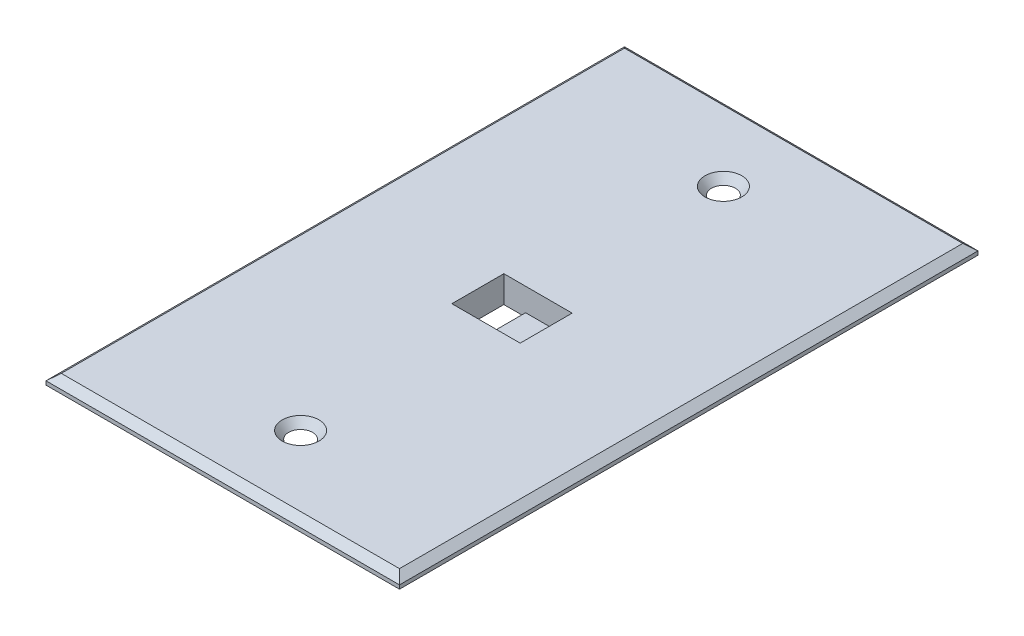
SolidWorks part; units mm, degrees
ref_plane "Front Plane" through (0, 0, 0) normal (0, 0, 1) x (1, 0, 0)
ref_plane "Top Plane" through (0, 0, 0) normal (0, 1, 0) x (1, 0, 0)
ref_plane "Right Plane" through (0, 0, 0) normal (1, 0, 0) x (0, 0, -1)
sketch "Sketch1" plane through (0, 0, 0) normal (0, 1, 0) x (1, 0, 0)
  line L1 (-34.675, 56.75) -> (34.675, 56.75)
  line L2 (-34.675, 56.75) -> (-34.675, -56.75)
  line L3 (-34.675, -56.75) -> (34.675, -56.75)
  line L4 (34.675, 56.75) -> (34.675, -56.75)
  line L5 (-34.675, 56.75) -> (34.675, -56.75) construction
  line L6 (-34.675, -56.75) -> (34.675, 56.75) construction
  point P0 (0, 0)
  dimension "D1" = 113.5
  dimension "D2" = 69.35
extrude "Boss-Extrude5" add sketch "Sketch1" along normal blind 2 contours L2 L1 L4 L3
sketch "Sketch2" plane through (0, 2, 0) normal (0, 1, 0) x (1, 0, 0)
  line L0 (0, 56.75) -> (0, -56.75) construction
  line L1 (-34.675, 56.75) -> (34.675, 56.75) construction
  line L2 (-34.675, -56.75) -> (34.675, -56.75) construction
  line L3 (-34.675, 0) -> (34.675, 0) construction
  line L4 (-34.675, 56.75) -> (-34.675, -56.75) construction
  line L5 (34.675, 56.75) -> (34.675, -56.75) construction
  circle A0 centre (0, 41.476) radius 2.35
  circle A1 centre (0, -41.476) radius 2.35
extrude "Cut-Extrude3" cut sketch "Sketch2" against normal blind 2.5
chamfer "face chamfer" distance 1.5 angle 40 6 edges at (0, 2, 39.126) (0, 2, -39.126) (0, 2, -56.75) (34.675, 2, 0) (0, 2, 56.75) (-34.675, 2, 0)
sketch "Sketch4" plane through (0, 0, 0) normal (0, -1, 0) x (-1, 0, 0)
  line L1 (-30.1192, 45.2572) -> (30.1192, 45.2572)
  line L2 (-30.1192, 45.2572) -> (-30.1192, -45.2572)
  line L3 (-30.1192, -45.2572) -> (30.1192, -45.2572)
  line L4 (30.1192, 45.2572) -> (30.1192, -45.2572)
  line L5 (-30.1192, 45.2572) -> (30.1192, -45.2572) construction
  line L6 (-30.1192, -45.2572) -> (30.1192, 45.2572) construction
  point P0 (0, 0)
extrude "Cut-Extrude6" cut sketch "Sketch4" against normal blind 0.5
sketch "Sketch5" plane through (0, 2, 0) normal (0, 1, 0) x (1, 0, 0)
  line L0 (-33.175, 0) -> (33.175, 0) construction
  line L1 (-33.175, 55.25) -> (-33.175, -55.25) construction
  line L2 (33.175, -55.25) -> (33.175, 55.25) construction
  line L3 (0, 55.25) -> (0, -56.75) construction
  line L4 (33.175, 55.25) -> (-33.175, 55.25) construction
  line L5 (34.675, -56.75) -> (-34.675, -56.75) construction
  line L7 (-6.7, 5.1) -> (6.7, 5.1)
  line L8 (-6.7, 5.1) -> (-6.7, -5.1)
  line L9 (-6.7, -5.1) -> (6.7, -5.1)
  line L10 (6.7, 5.1) -> (6.7, -5.1)
  line L11 (-6.7, 5.1) -> (6.7, -5.1) construction
  line L12 (-6.7, -5.1) -> (6.7, 5.1) construction
  line L13 (10.4666, 8.5495) -> (-10.4666, 8.5495)
  line L14 (10.4666, 8.5495) -> (10.4666, -8.5495)
  line L15 (10.4666, -8.5495) -> (-10.4666, -8.5495)
  line L16 (-10.4666, 8.5495) -> (-10.4666, -8.5495)
  line L17 (10.4666, 8.5495) -> (-10.4666, -8.5495) construction
  line L18 (10.4666, -8.5495) -> (-10.4666, 8.5495) construction
  point P12 (0, 0)
  point P17 (0, 0)
  dimension "D1" = 13.4
  dimension "D2" = 10.2
extrude "Boss-Extrude7" add sketch "Sketch5" against normal blind 4.5
sketch "Sketch6" plane through (0, 2, 0) normal (0, 1, 0) x (1, 0, 0)
  line L0 (0, 55.25) -> (0, -56.75) construction
  line L1 (33.175, 55.25) -> (-33.175, 55.25) construction
  line L2 (34.675, -56.75) -> (-34.675, -56.75) construction
  line L3 (-34.675, 0) -> (34.675, 0) construction
  line L4 (-34.675, -56.75) -> (-34.675, 56.75) construction
  line L5 (34.675, 56.75) -> (34.675, -56.75) construction
  line L7 (-6.7, 5.1) -> (6.7, 5.1)
  line L8 (-6.7, 5.1) -> (-6.7, -5.1)
  line L9 (-6.7, -5.1) -> (6.7, -5.1)
  line L10 (6.7, 5.1) -> (6.7, -5.1)
  line L11 (-6.7, 5.1) -> (6.7, -5.1) construction
  line L12 (-6.7, -5.1) -> (6.7, 5.1) construction
  point P12 (0, 0)
  dimension "D1" = 13.4
  dimension "D2" = 10.2
extrude "Cut-Extrude7" cut sketch "Sketch6" against normal blind 4.1
sketch "Sketch7" plane through (0, -2.5, 0) normal (0, -1, 0) x (1, 0, 0)
  line L1 (-10.4666, 8.5495) -> (10.4666, 8.5495)
  line L2 (-10.4666, 8.5495) -> (-10.4666, -8.5495)
  line L3 (-10.4666, -8.5495) -> (10.4666, -8.5495)
  line L4 (10.4666, 8.5495) -> (10.4666, -8.5495)
  line L5 (-10.4666, 8.5495) -> (10.4666, -8.5495) construction
  line L6 (-10.4666, -8.5495) -> (10.4666, 8.5495) construction
  point P0 (0, 0)
extrude "Boss-Extrude8" add sketch "Sketch7" along normal blind 0.75
sketch "Sketch8" plane through (0, -2.5, 0) normal (0, 1, 0) x (1, 0, 0)
  line L0 (-6.7, -5.1) -> (6.7, -5.1) construction
  line L1 (-6.7, 5.1) -> (-4.0786, 5.1)
  line L2 (-6.7, 5.1) -> (-6.7, -5.1)
  line L3 (-6.7, -5.1) -> (-4.0786, -5.1)
  line L4 (-4.0786, 5.1) -> (-4.0786, -5.1)
extrude "Cut-Extrude8" cut sketch "Sketch8" against normal blind 0.5
ref_plane "Plane4" through (6.7, 0, 0) normal (1, 0, 0) x (0, 0, -1)
sketch "Sketch10" plane through (6.7, 0, 0) normal (-1, 0, 0) x (0, 0, 1)
  line L0 (0, 2) -> (0, -2.5) construction
  line L1 (5.1, 2) -> (-5.1, 2) construction
  line L2 (5.1, -2.5) -> (-5.1, -2.5) construction
  line L3 (-5.1, 0.3) -> (5.1, 0.3) construction
  line L4 (-5.1, -2.5) -> (-5.1, 2) construction
  line L5 (5.1, -2.5) -> (5.1, 2) construction
  line L7 (-0.6375, 0.3) -> (0.5457, 0.3)
  line L8 (-0.6375, 0.3) -> (-0.6375, 0.9608)
  line L9 (-0.6375, 0.9608) -> (0.5457, 0.9608)
  line L10 (0.5457, 0.3) -> (0.5457, 0.9608)
  dimension "D1" = 2.8
extrude "Boss-Extrude11" add sketch "Sketch10" along normal blind 1
fillet "Fillet1" radius 0.9 1 edges at (5.7, 0.9608, -0.0459)
sketch "Sketch11" plane through (0, -3.25, 0) normal (0, -1, 0) x (-1, 0, 0)
  line L1 (6.7, -5.1) -> (2.4368, -5.1)
  line L2 (6.7, -5.1) -> (6.7, 5.1)
  line L3 (6.7, 5.1) -> (2.4368, 5.1)
  line L4 (2.4368, -5.1) -> (2.4368, 5.1)
extrude "Cut-Extrude9" cut sketch "Sketch11" against normal blind 10
